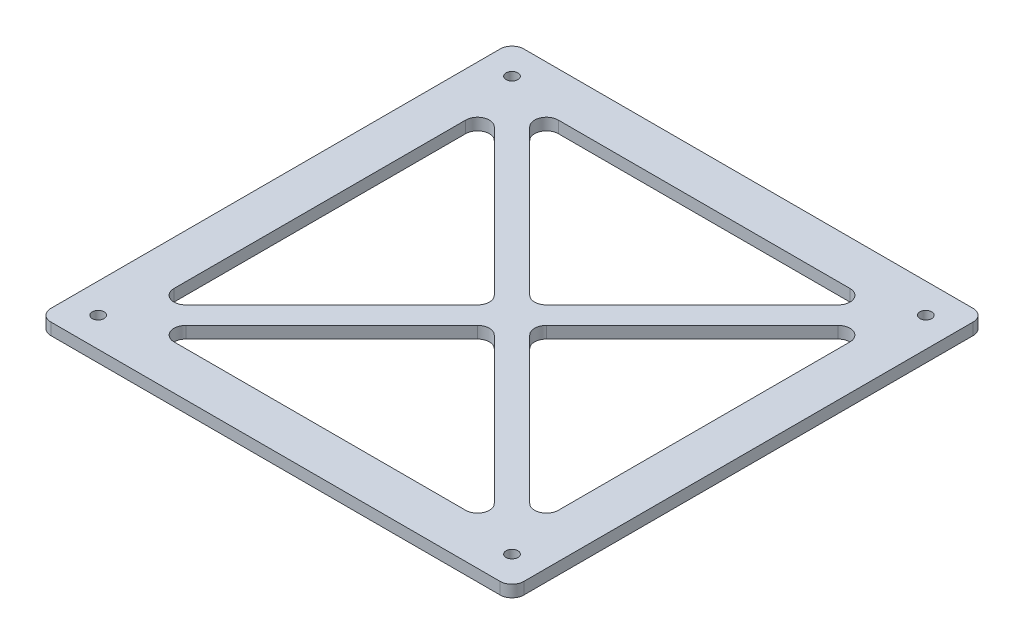
SolidWorks part; units mm, degrees
ref_plane "前基準面" through (0, 0, 0) normal (0, 0, 1) x (1, 0, 0)
ref_plane "上基準面" through (0, 0, 0) normal (0, 1, 0) x (1, 0, 0)
ref_plane "右基準面" through (0, 0, 0) normal (1, 0, 0) x (0, 0, -1)
sketch "草圖1" plane through (0, 0, 0) normal (0, 1, 0) x (1, 0, 0)
  line L0 (-52.5, 52.5) -> (52.5, 52.5) construction
  line L1 (-60, 60) -> (60, 60)
  line L2 (-60, 60) -> (-60, -60)
  line L3 (-60, -60) -> (60, -60)
  line L4 (60, 60) -> (60, -60)
  line L5 (-60, 60) -> (60, -60) construction
  line L6 (-60, -60) -> (60, 60) construction
  line L7 (-52.5, 52.5) -> (-52.5, -52.5) construction
  line L8 (-52.5, 52.5) -> (-52.5, 60) construction
  line L9 (-52.5, 52.5) -> (-60, 52.5) construction
  circle A0 centre (-52.5, 52.5) radius 1.5
  circle A1 centre (52.5, 52.5) radius 1.5
  circle A2 centre (52.5, -52.5) radius 1.5
  circle A3 centre (-52.5, -52.5) radius 1.5
  point P0 (0, 0)
  dimension "D7" = 3
  dimension "D1" = 120
  dimension "D2" = 120
  dimension "D5" = 105
  dimension "D6" = 105
  dimension "D8" = 7.5
  dimension "D3" = 2
  dimension "D4" = 2
extrude "填料-伸長1" add sketch "草圖1" along normal blind 3
sketch "草圖2" plane through (0, 3, 0) normal (0, 1, 0) x (1, 0, 0)
  line L0 (0, 0) -> (55.2066, 0) construction
  line L1 (55.2066, 0) -> (-60.768, 0) construction
  line L2 (0, 0) -> (0, 56.6444) construction
  line L3 (0, 56.6444) -> (0, -55.3423) construction
  line L5 (-48.75, 48.75) -> (48.75, 48.75)
  line L6 (-48.75, 48.75) -> (-48.75, -48.75)
  line L7 (-48.75, -48.75) -> (48.75, -48.75)
  line L8 (48.75, 48.75) -> (48.75, -48.75)
  line L9 (-48.75, 48.75) -> (48.75, -48.75) construction
  line L10 (-48.75, -48.75) -> (48.75, 48.75) construction
  dimension "D1" = 97.5
  dimension "D2" = 97.5
sketch "草圖3" plane through (0, 3, 0) normal (0, 1, 0) x (1, 0, 0)
  line L0 (-48.75, 44.25) -> (-4.5, 0)
  line L1 (-48.75, 48.75) -> (-48.75, -48.75) construction
  line L2 (55.2066, 0) -> (-60.768, 0) construction
  line L3 (-4.5, 0) -> (-48.75, -44.25)
  line L4 (-48.75, -44.25) -> (-48.75, 44.25)
  line L5 (-48.75, -48.75) -> (48.75, 48.75) construction
  line L6 (-48.75, 48.75) -> (48.75, -48.75) construction
  line L7 (-44.25, 48.75) -> (44.25, 48.75)
  line L8 (44.25, 48.75) -> (0, 4.5)
  line L9 (0, 4.5) -> (-44.25, 48.75)
  line L10 (48.75, 44.25) -> (48.75, -44.25)
  line L11 (48.75, -44.25) -> (4.5, 0)
  line L12 (4.5, 0) -> (48.75, 44.25)
  line L13 (44.25, -48.75) -> (-44.25, -48.75)
  line L14 (-44.25, -48.75) -> (0, -4.5)
  line L15 (0, -4.5) -> (44.25, -48.75)
  point P24 (0, 0)
  dimension "D1" = 4.5
  dimension "D2" = 4
extrude "除料-伸長1" cut sketch "草圖3" against normal through all
fillet "圓角1" radius 3 16 edges at (44.25, 1.5, 48.75) (0, 1.5, 4.5) (-44.25, 1.5, 48.75) (48.75, 1.5, 44.25) (4.5, 1.5, 0) (48.75, 1.5, -44.25) (0, 1.5, -4.5) (-44.25, 1.5, -48.75) (44.25, 1.5, -48.75) (-48.75, 1.5, 44.25) (-48.75, 1.5, -44.25) (-4.5, 1.5, 0) (-60, 1.5, 60) (60, 1.5, 60) (-60, 1.5, -60) (60, 1.5, -60)
